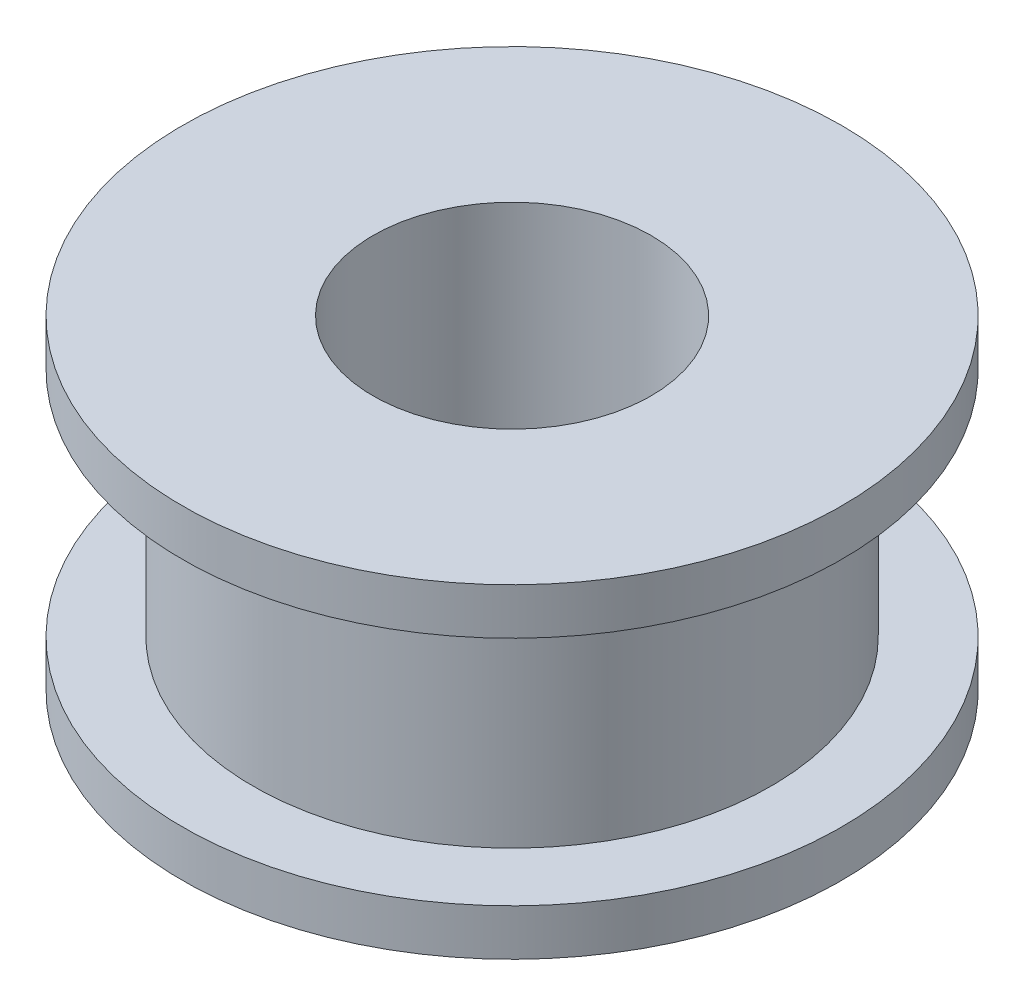
SolidWorks part; units mm, degrees
material "6061-T6 (SS)"
ref_plane "Front Plane" through (0, 0, 0) normal (1, 0, 0) x (0, 1, 0)
ref_plane "Top Plane" through (0, 0, 0) normal (0, 0, 1) x (0, 1, 0)
ref_plane "Right Plane" through (0, 0, 0) normal (0, 1, 0) x (-1, 0, 0)
sketch "Sketch1" plane through (0, 0, 0) normal (1, 0, 0) x (0, 1, 0)
  line L0 (-39.0416, 0) -> (31.6415, 0) construction
  line L1 (0, 3) -> (-7, 3)
  line L2 (-7, 3) -> (-7, 7.112)
  line L3 (-7, 7.112) -> (-6, 7.112)
  line L4 (-6, 7.112) -> (-6, 5.588)
  line L5 (-6, 5.588) -> (-1, 5.588)
  line L6 (-1, 5.588) -> (-1, 7.112)
  line L7 (-1, 7.112) -> (0, 7.112)
  line L8 (0, 7.112) -> (0, 3)
  dimension "D1" = 3
  dimension "D2" = 5.588
  dimension "D4" = 1.524
  dimension "D5" = 5
  dimension "D6" = 1
  dimension "D7" = 1
revolve "Revolve1" add sketch "Sketch1" angle 360 about L0
equation "\"D1@Sketch1\"=3mm"
equation "\"D5@Sketch1\"=5mm"
equation "\"D6@Sketch1\"=1mm"
equation "\"D7@Sketch1\"=1mm"
